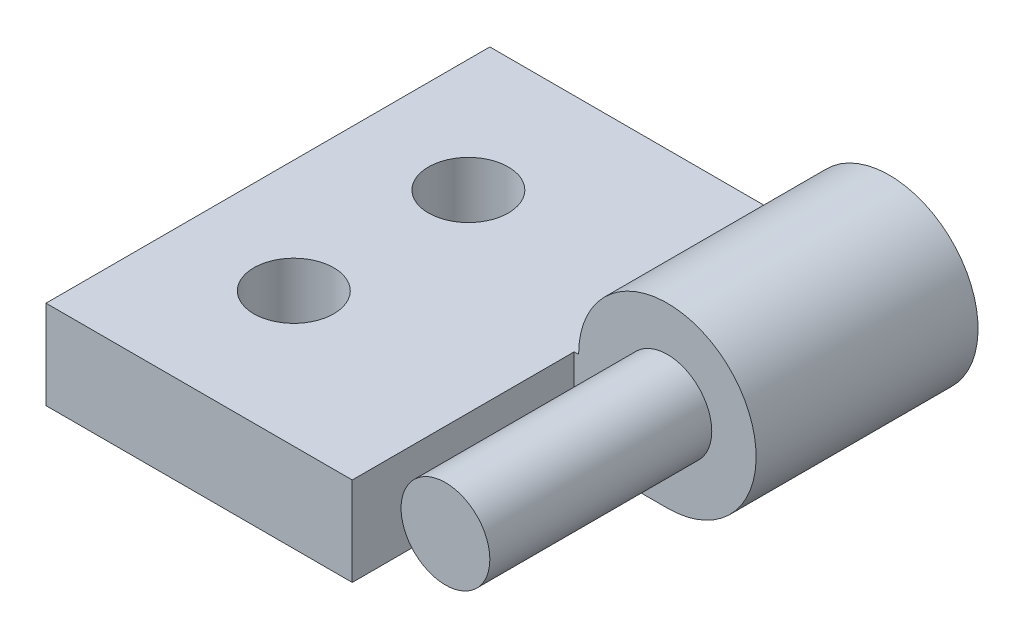
SolidWorks part; units mm, degrees
ref_plane "Front Plane" through (0, 0, 0) normal (0, 0, 1) x (1, 0, 0)
ref_plane "Top Plane" through (0, 0, 0) normal (0, 1, 0) x (1, 0, 0)
ref_plane "Right Plane" through (0, 0, 0) normal (1, 0, 0) x (0, 0, -1)
sketch "Sketch1" plane through (0, 0, 0) normal (0, 0, 1) x (1, 0, 0)
  line L0 (0, 0) -> (0, 5.08)
  line L1 (0, 0) -> (22.86, 0)
  line L5 (0, 5.08) -> (17.78, 5.08)
  arc A0 (22.86, 0) -> (17.78, 5.08) centre (22.86, 5.08) ccw
  point P1 (0, 0)
  dimension "D1" = 10.16
  dimension "D2" = 5.08
  dimension "D3" = 17.78
extrude "Boss-Extrude1" add sketch "Sketch1" along normal blind 25.4
sketch "Sketch2" plane through (0, 0, 25.4) normal (0, 0, 1) x (1, 0, 0)
  line L0 (17.526, 5.08) -> (17.526, 0)
  line L1 (0, 0) -> (22.86, 0) construction
  line L2 (17.526, 0) -> (21.2336, 0)
  arc A0 (21.2336, 0) -> (17.526, 5.08) centre (22.86, 5.08) ccw
  circle A1 centre (22.86, 5.08) radius 2.54
  dimension "D1" = 5.08
  dimension "D2" = 10.668
extrude "Cut-Extrude1" cut sketch "Sketch2" against normal blind 12.7
sketch "Sketch3" plane through (0, 5.08, 0) normal (0, 1, 0) x (1, 0, 0)
  line L0 (6.477, -5.4187) -> (6.477, 0) construction
  line L1 (17.78, 0) -> (0, 0) construction
  line L2 (6.477, -9.9907) -> (6.477, -15.4093) construction
  line L3 (6.477, -19.9813) -> (6.477, -25.4) construction
  line L5 (17.526, -25.4) -> (0, -25.4) construction
  line L6 (17.78, -12.7) -> (17.78, 0) construction
  circle A0 centre (6.477, -7.7047) radius 2.286
  circle A1 centre (6.477, -17.6953) radius 2.286
  point P12 (8.5395, -25.4)
  dimension "D1" = 4.572
  dimension "D2" = 11.303
extrude "Cut-Extrude2" cut sketch "Sketch3" against normal through all
